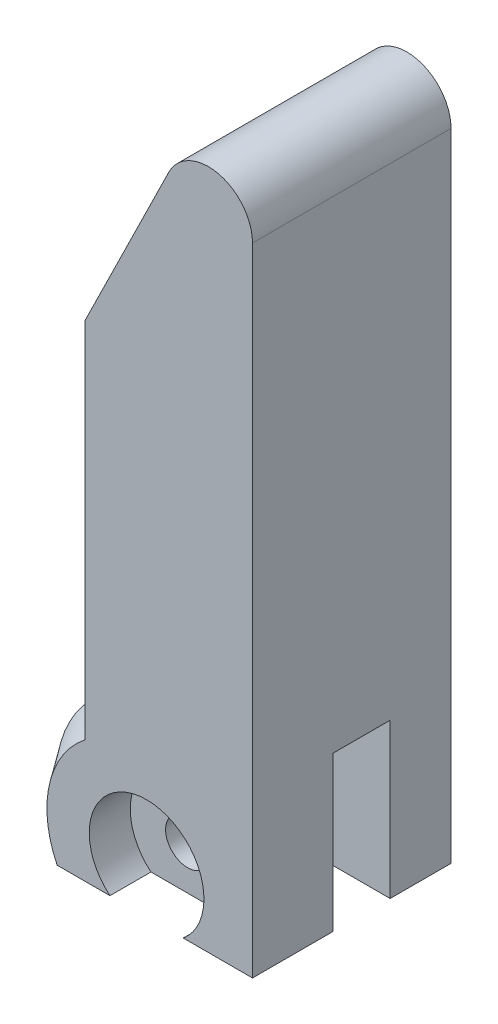
SolidWorks part; units mm, degrees
ref_plane "前视基准面" through (0, 0, 0) normal (0, 0, 1) x (1, 0, 0)
ref_plane "上视基准面" through (0, 0, 0) normal (0, 1, 0) x (1, 0, 0)
ref_plane "右视基准面" through (0, 0, 0) normal (1, 0, 0) x (0, 0, -1)
sketch "草图1" plane through (0, 0, 0) normal (0, 0, 1) x (1, 0, 0)
  line L0 (0, 0) -> (0, 144.2721)
  line L2 (-49.6174, 0) -> (0, 0)
  line L3 (-18.9734, 148.6855) -> (-38, 110)
  line L4 (-38, 110) -> (-38, 33.6696)
  arc A0 (0, 144.2721) -> (-18.9734, 148.6855) centre (-10, 144.2721) ccw
  arc A1 (-38, 33.6696) -> (-49.6174, 0) centre (-24, 10) ccw
  dimension "D2" = 10
  dimension "D4" = 27.5
  dimension "D1" = 135
  dimension "D3" = 10
  dimension "D5" = 38
  dimension "D6" = 24
  dimension "D7" = 100
extrude "凸台-拉伸1" add sketch "草图1" along normal blind 45
ref_axis "基准轴1" through (-24, 10, 45) along (0, 0, -1)
ref_plane "基准面1" through (-24, 0, 0) normal (1, 0, 0) x (0, 0, -1)
sketch "草图2" plane through (-24, 0, 0) normal (1, 0, 0) x (0, 0, -1)
  line L0 (-45, 10) -> (0, 10) construction
  line L1 (-45, 10) -> (0, 10) construction
  line L2 (-45, 0) -> (-45, 144.2721) construction
  line L3 (-45, 10) -> (-45, 23)
  line L4 (-35.7, 23) -> (-35.7, 15)
  line L5 (-30.3, 12.5) -> (-26.3, 12.5)
  line L6 (-26.3, 12.5) -> (-26.3, 14)
  line L7 (-35.7, 23) -> (-45, 23)
  line L8 (-45, 23) -> (-45, 10)
  line L9 (0, 10) -> (-45, 10)
  line L10 (-45, 10) -> (-45, 23)
  line L11 (-26.3, 14) -> (-26.8, 14)
  line L12 (-10.3, 12.5) -> (-10.3, 15)
  line L13 (-26.8, 14) -> (-26.8, 35)
  line L14 (-26.8, 35) -> (-13.8, 35)
  line L15 (-13.8, 35) -> (-13.8, 14)
  line L16 (-13.8, 14) -> (-14.3, 14)
  line L17 (-14.3, 14) -> (-14.3, 12.5)
  line L18 (-14.3, 12.5) -> (-10.3, 12.5)
  line L19 (-35.7, 15) -> (-30.3, 15)
  line L20 (-30.3, 15) -> (-30.3, 12.5)
  line L21 (-10.3, 15) -> (-4.3, 15)
  line L22 (-4.3, 15) -> (-4.3, 30)
  line L23 (-4.3, 30) -> (0, 30)
  line L24 (0, 0) -> (0, 144.2721) construction
  line L25 (0, 30) -> (0, 10)
  dimension "D1" = 12
  dimension "D2" = 4
  dimension "D3" = 5
  dimension "D4" = 2.5
  dimension "D5" = 18.7
  dimension "D6" = 35.7
  dimension "D7" = 4
  dimension "D8" = 0.5
  dimension "D9" = 4
  dimension "D10" = 6
  dimension "D11" = 13
  dimension "D12" = 20
  dimension "D13" = 25
  dimension "D14" = 5
revolve "切除-旋转2" cut sketch "草图2" angle 360 about L0 region at (-24, 19.7005, 21.6491)
chamfer "倒角1" distance 7 angle 35 2 edges at (-49.9961, 18.9697, 0) (-49.9961, 18.9697, 45) first distance on face at (-46.9024, 17.9022, 22.5)
sketch "草图4" plane through (0, 0, 13.8) normal (0, 0, 1) x (1, 0, 0)
  line L0 (-24, 35) -> (0, 35)
  line L1 (0, 0) -> (0, 144.2721) construction
  line L2 (0, 35) -> (0, 17)
  line L3 (-1.0871, 0) -> (0, 0)
  line L4 (0, 0) -> (0, 3)
  arc A0 (-1.0871, 0) -> (0, 3) centre (-24, 10) ccw construction
  arc A1 (0, 17) -> (-46.9129, 0) centre (-24, 10) ccw construction
  arc A2 (-1.0871, 0) -> (0, 3) centre (-24, 10) ccw
  arc A3 (0, 17) -> (-24, 35) centre (-24, 10) ccw
extrude "切除-拉伸1" cut sketch "草图4" along normal up to surface (13 mm away) up to face at (-20, 10, 26.8)
